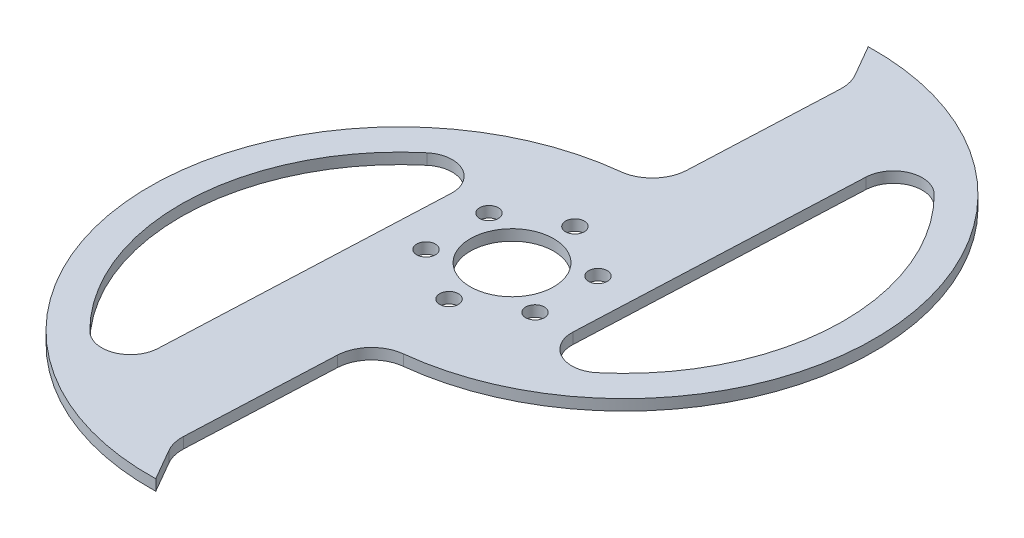
SolidWorks part; units mm, degrees
ref_plane "Front Plane" through (0, 0, 0) normal (0, 0, 1) x (1, 0, 0)
ref_plane "Top Plane" through (0, 0, 0) normal (0, 1, 0) x (1, 0, 0)
ref_plane "Right Plane" through (0, 0, 0) normal (1, 0, 0) x (0, 0, -1)
ref_axis "Axis1" through (0, -0.15, 0) along (0, 1, 0)
sketch "Sketch1" plane through (0, 0, 0) normal (0, 1, 0) x (1, 0, 0)
  line L1 (0, -17.5) -> (15.1554, -8.75) construction
  line L2 (15.1554, -8.75) -> (15.1554, 8.75) construction
  line L3 (15.1554, 8.75) -> (0, 17.5) construction
  line L4 (0, 17.5) -> (-15.1554, 8.75) construction
  line L5 (-15.1554, 8.75) -> (-15.1554, -8.75) construction
  line L6 (-15.1554, -8.75) -> (0, -17.5) construction
  circle A0 centre (0, 0) radius 15.1554 construction
  circle A1 centre (15.1554, -8.75) radius 2.6
  circle A2 centre (0, -17.5) radius 2.6
  circle A3 centre (-15.1554, -8.75) radius 2.6
  circle A4 centre (-15.1554, 8.75) radius 2.6
  circle A5 centre (0, 17.5) radius 2.6
  circle A6 centre (15.1554, 8.75) radius 2.6
  circle A7 centre (0, 0) radius 11.6
  circle A8 centre (0, 0) radius 101.6 construction
  dimension "D1" = 5.2
  dimension "D2" = 23.2
  dimension "D3" = 203.2
  dimension "D4" = 35
sketch "Sketch2" plane through (0, 0, 0) normal (0, 1, 0) x (1, 0, 0)
  line L0 (0, -1000) -> (0, 49000) construction
  line L1 (-2.5, 101.5692) -> (2.5, 92.909)
  line L2 (0, 0) -> (35355.3391, 35355.3391) construction
  line L3 (3.8302, 87.4715) -> (1.4901, 34.0298)
  line L4 (-1000, 0) -> (49000, 0) construction
  line L5 (28.5845, 69.8837) -> (25.4756, -1.1155) construction
  line L8 (28.5845, 69.8837) -> (25.166, -8.1854)
  line L9 (87.4715, -3.8302) -> (34.0298, -1.4901) construction
  line L11 (-3.8302, -87.4715) -> (-1.4901, -34.0298) construction
  line L12 (-87.4715, 3.8302) -> (-34.0298, 1.4901) construction
  line L13 (-1.6405, -37.4641) -> (-1.1155, -25.4756)
  circle A0 centre (0, 0) radius 101.6 construction
  arc A1 (-2.5, 101.5692) -> (28.5845, 69.8837) centre (-1.7528, 71.2121) cw construction
  circle A3 centre (0, 0) radius 79.6 construction
  circle A5 centre (0, 0) radius 25.5 construction
  arc A20 (-2.5, 101.5692) -> (0, 0) centre (-49.5947, 49.5947) cw construction
  arc A21 (2.5, 92.909) -> (3.8302, 87.4715) centre (-6.1603, 87.909) cw
  arc A25 (1.4901, 34.0298) -> (-6.1059, 24.7582) centre (-8.5003, 34.4673) cw
  arc A27 (-2.5, 101.5692) -> (-1.6405, -37.4641) centre (-0.7891, 32.0605) cw
  arc A28 (28.5845, 69.8837) -> (42.2256, 75.1987) centre (36.5768, 69.5337) cw
  arc A29 (42.2256, 75.1987) -> (38.2903, -14.6724) centre (-0.7891, 32.0605) cw
  arc A30 (38.2903, -14.6724) -> (25.166, -8.1854) centre (33.1584, -8.5354) cw
  circle A32 centre (0, 0) radius 11.6 construction
  arc A34 (-1.1155, -25.4756) -> (-6.1059, 24.7582) centre (0, 0) cw
  point P7 (0, 97.2391)
  point P16 (-79.6, 0)
  point P17 (-101.6, 0)
  point P21 (25.5, 0)
  point P39 (0, 0)
  point P48 (0, 0)
  point P50 (-1.1155, -25.4756)
  dimension "D3" = 45
  dimension "D8" = 8
  dimension "D7" = 10
  dimension "D5" = 51
  dimension "D1" = 30
  dimension "D2" = 22
  dimension "D4" = 10
  dimension "D6" = 25.5
  dimension "D9" = 4
  dimension "D10" = 12
extrude "Boss-Extrude1" add sketch "Sketch2" along normal blind 3.02
pattern_circular "CirPattern1" count 2 over 360 about axis through (0, -0.15, 0) along (0, 1, 0) of bodies 101
combine bodies "Combine1" bodies to combine 101 102
extrude "Cut-Extrude3" cut sketch "Sketch1" along normal through all
fillet "Fillet2" radius 10 2 edges at (-1.6405, 1.51, 37.4641) (1.6405, 1.51, -37.4641)
